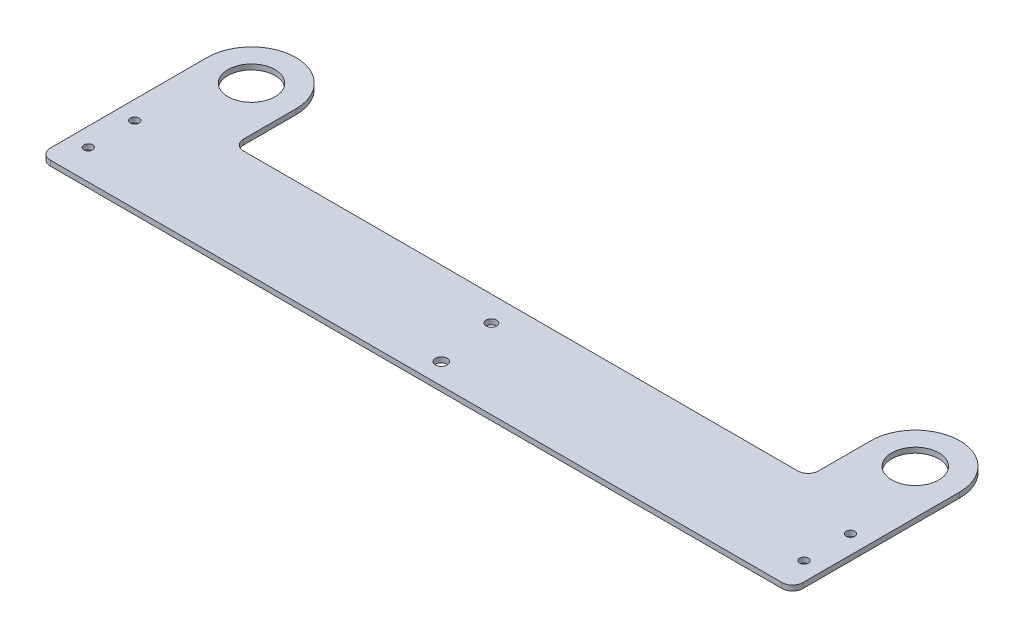
SolidWorks part; units mm, degrees
material "6063-T6"
ref_plane "Front" through (0, 0, 0) normal (0, 0, 1) x (1, 0, 0)
ref_plane "Top" through (0, 0, 0) normal (0, 1, 0) x (1, 0, 0)
ref_plane "Right" through (0, 0, 0) normal (1, 0, 0) x (0, 0, -1)
sketch "Sketch1" plane through (0, 0, 0) normal (0, 1, 0) x (1, 0, 0)
  line L0 (0, 0) -> (403.225, 0) construction
  line L5 (-26.9875, 0) -> (-26.9875, -95.25)
  line L6 (430.2125, 0) -> (430.2125, -95.25)
  line L7 (423.8625, -101.6) -> (-20.6375, -101.6)
  line L8 (26.9875, 0) -> (26.9875, -31.75)
  line L9 (376.2375, 0) -> (376.2375, -31.75)
  line L10 (369.8875, -38.1) -> (33.3375, -38.1)
  line L11 (403.225, 0) -> (403.225, 26.9875) construction
  circle A0 centre (0, 0) radius 14.2875
  circle A1 centre (403.225, 0) radius 14.2875
  arc A2 (26.9875, 0) -> (-26.9875, 0) centre (0, 0) ccw
  arc A3 (430.2125, 0) -> (376.2375, 0) centre (403.225, 0) ccw
  circle A4 centre (0, 0) radius 26.9875 construction
  circle A5 centre (403.225, 0) radius 26.9875 construction
  arc A6 (376.2375, -31.75) -> (369.8875, -38.1) centre (369.8875, -31.75) cw
  arc A7 (430.2125, -95.25) -> (423.8625, -101.6) centre (423.8625, -95.25) cw
  arc A8 (-26.9875, -95.25) -> (-20.6375, -101.6) centre (-20.6375, -95.25) ccw
  arc A9 (26.9875, -31.75) -> (33.3375, -38.1) centre (33.3375, -31.75) ccw
  point P24 (-26.9875, -101.6)
  point P27 (26.9875, -38.1)
  dimension "D3" = 28.575
  dimension "D5" = 28.575
  dimension "D7" = 6.35
  dimension "D9" = 128.5875
  dimension "D1" = 12.7
  dimension "D2" = 101.6
  dimension "D4" = 403.225
  dimension "D6" = 38.1
  dimension "D8" = 457.2
extrude "Boss-Extrude1" add sketch "Sketch1" along normal blind 3.175
sketch "Sketch2" plane through (0, 3.175, 0) normal (0, 1, 0) x (1, 0, 0)
  line L1 (-26.9875, 0) -> (-26.9875, -95.25) construction
  line L2 (-20.6375, -101.6) -> (423.8625, -101.6) construction
  line L3 (430.2125, -95.25) -> (430.2125, 0) construction
  circle A1 centre (204.1525, -88.9) radius 3.556
  circle A3 centre (199.0725, -53.34) radius 3.175
  dimension "D3" = 231.14
  dimension "D1" = 231.14
  dimension "D2" = 12.7
  dimension "D4" = 48.26
extrude "Cut-Extrude1" cut sketch "Sketch2" against normal up to next
sketch "Sketch3" plane through (0, 3.175, 0) normal (0, 1, 0) x (1, 0, 0)
  line L0 (201.6125, -38.1) -> (201.6125, 7.4644) construction
  line L1 (369.8875, -38.1) -> (33.3375, -38.1) construction
  circle A1 centre (-15.7797, -55.159) radius 2.667
  circle A2 centre (419.0047, -55.159) radius 2.667
  circle A3 centre (-15.7797, -83.3715) radius 2.667
  circle A4 centre (419.0047, -83.3715) radius 2.667
  dimension "D1" = 5.334
extrude "Cut-Extrude2" cut sketch "Sketch3" against normal up to next
